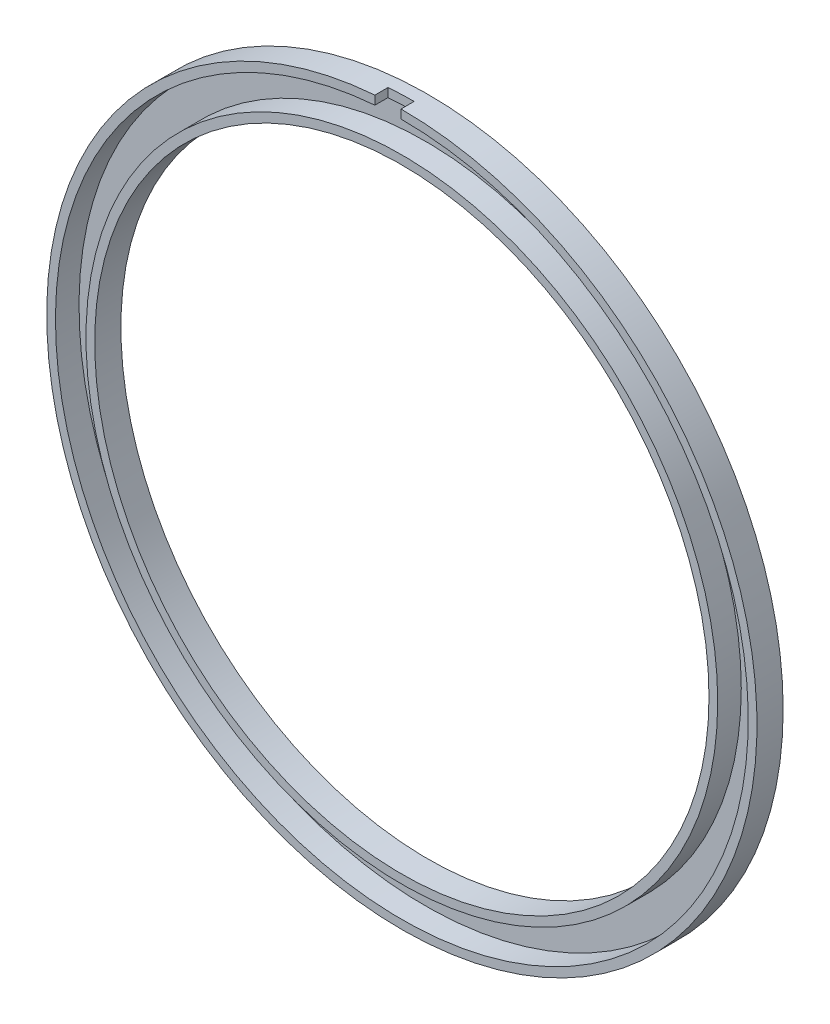
SolidWorks part; units mm, degrees
ref_plane "Front Plane" through (0, 0, 0) normal (0, 0, 1) x (1, 0, 0)
ref_plane "Top Plane" through (0, 0, 0) normal (0, 1, 0) x (1, 0, 0)
ref_plane "Right Plane" through (0, 0, 0) normal (1, 0, 0) x (0, 0, -1)
sketch "Sketch1" plane through (0, 0, 0) normal (0, 0, 1) x (1, 0, 0)
  line L1 (-6.1827, 81.1649) -> (-6.1827, 79.1589)
  line L2 (-0.1873, 81.3998) -> (-0.1827, 79.3998)
  circle A0 centre (0, 0) radius 72.4
  circle A1 centre (0, 0) radius 81.4
  circle A2 centre (0, 0) radius 79.4
  circle A3 centre (0, 0) radius 70.4
  point P4 (81.4, 0)
  point P5 (-81.4, 0)
  point P6 (-72.4, 0)
  point P7 (72.4, 0)
  point P9 (-79.4, 0)
  point P10 (79.4, 0)
  point P12 (70.4, 0)
  point P13 (-70.4, 0)
  dimension "D1" = 162.8
  dimension "D2" = 2
  dimension "D3" = 7
  dimension "D4" = 2
  dimension "D5" = 6
  dimension "D6" = 6
extrude "Boss-Extrude1" add sketch "Sketch1" along normal blind 0.6 contours A2 A0 region at (-3.0948, 77.0921, 0)
extrude "Boss-Extrude2" add sketch "Sketch1<3>" along normal blind 6 contours A0 A3 | A1 A2 region at (-8.485, 80.1619, 0) region at (-72.1952, 0, 0)
sketch "Sketch1<3>" plane through (0, 0, 0) normal (0, 0, 1) x (1, 0, 0) same geometry as "Sketch1"
extrude "Boss-Extrude3" add sketch "Sketch1<4>" along normal blind 3 contours A2 L2 A1 L1 region at (-3.1853, 80.318, 0)
sketch "Sketch1<4>" plane through (0, 0, 0) normal (0, 0, 1) x (1, 0, 0) same geometry as "Sketch1"
